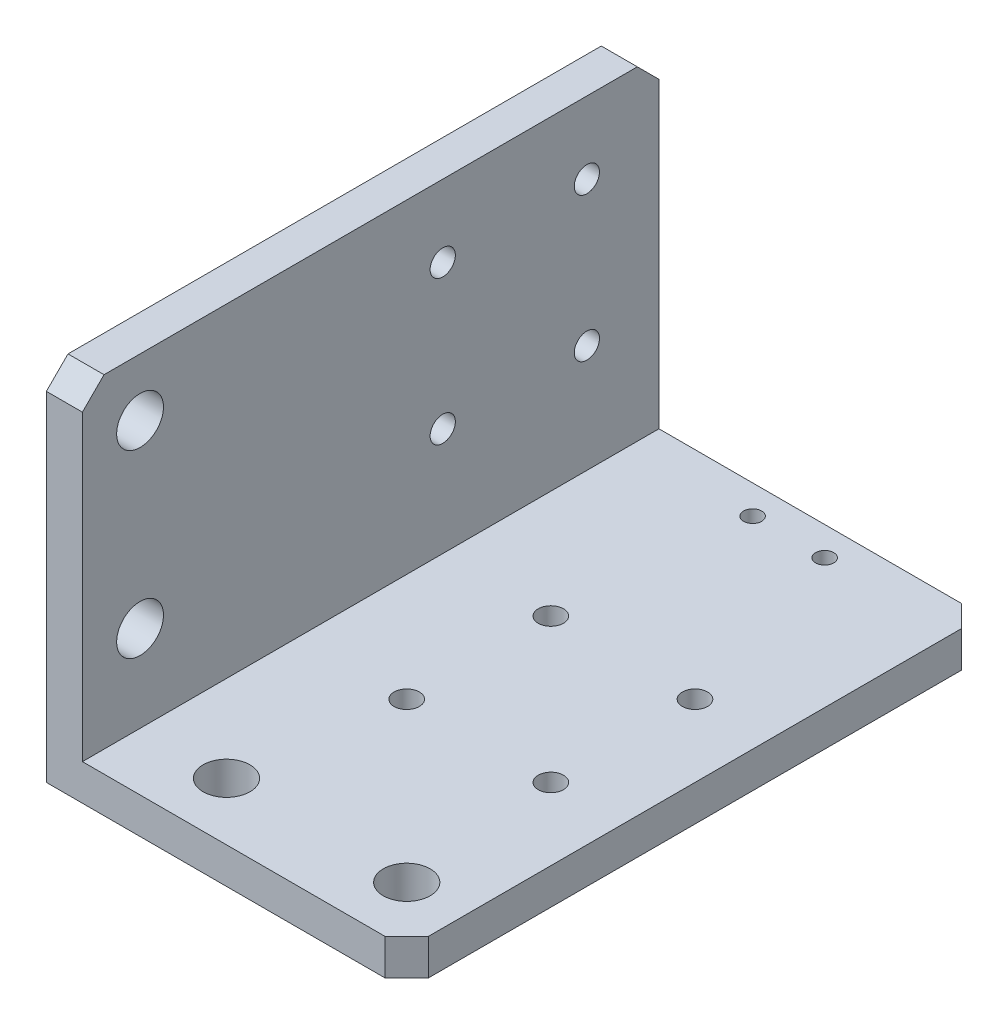
SolidWorks part; units mm, degrees
material "Lega 1060"
ref_plane "Piano frontale" through (0, 0, 0) normal (0, 0, 1) x (1, 0, 0)
ref_plane "Piano superiore" through (0, 0, 0) normal (0, 1, 0) x (1, 0, 0)
ref_plane "Piano destro" through (0, 0, 0) normal (1, 0, 0) x (0, 0, -1)
sketch "Schizzo1" plane through (0, 0, 0) normal (0, 0, 1) x (1, 0, 0)
  line L0 (0, 0) -> (0, 50)
  line L1 (0, 50) -> (5, 50)
  line L2 (5, 50) -> (5, 5)
  line L3 (5, 5) -> (50, 5)
  line L4 (50, 5) -> (50, 0)
  line L5 (50, 0) -> (0, 0)
  dimension "D1" = 5
  dimension "D2" = 5
  dimension "D3" = 50
  dimension "D4" = 50
extrude "Estrusione-Estrusione1" add sketch "Schizzo1" along normal blind 80
sketch "Schizzo2" plane through (0, 0, 0) normal (0, -1, 0) x (1, 0, 0)
  line L0 (5.4524, 72) -> (42.7933, 72) construction
  line L1 (0, 80) -> (50, 80) construction
  line L5 (50, 80) -> (50, 0) construction
  point P4 (17, 72)
  point P5 (42, 72)
  dimension "D1" = 8
  dimension "D2" = 25
  dimension "D3" = 8
sketch "Schizzo3" plane through (0, 0, 0) normal (-1, 0, 0) x (0, 0, 1)
  line L0 (72, 44.621) -> (72, 5.772) construction
  line L1 (80, 50) -> (80, 0) construction
  line L2 (80, 50) -> (0, 50) construction
  point P4 (72, 42)
  point P5 (72, 17)
  dimension "D1" = 8
  dimension "D2" = 8
  dimension "D3" = 25
hole_wizard "Foro Ø6.5 (6.5)-1" positions "Schizzo5" profile "Schizzo4" hole size "Ø6.5" standard "ISO" end condition through all
sketch "Schizzo5" plane through (0, 0, 0) normal (0, -1, 0) x (-1, 0, 0)
  point P0 (-17, -72)
  point P3 (-42, -72)
sketch "Schizzo4" plane through (17, 0, 72) normal (1, 0, 0) x (0, 0, -1)
  line L0 (0, 0) -> (0, 50)
  line L1 (0, 50) -> (3.25, 50)
  line L2 (3.25, 50) -> (3.25, 0)
  line L5 (3.25, 0) -> (0, 0)
  line L11 (0, -6.35) -> (0, 107.95) construction
  dimension "Thru Hole Dia." = 6.5
  dimension "Thru Hole Depth" = 50
hole_wizard "Foro Ø6.5 (6.5)-2" positions "Schizzo7" profile "Schizzo6" hole size "Ø6.5" standard "ISO"
sketch "Schizzo7" plane through (0, 0, 0) normal (-1, 0, 0) x (0, 0, 1)
  point P1 (72, 42)
  point P4 (72, 17)
sketch "Schizzo6" plane through (0, 42, 72) normal (0, 1, 0) x (0, 0, 1)
  line L0 (0, 0) -> (0, 6.9528)
  line L1 (0, 6.9528) -> (3.25, 5)
  line L2 (3.25, 5) -> (3.25, 0)
  line L5 (3.25, 0) -> (0, 0)
  line L10 (0, 6.9528) -> (-3.25, 5) construction
  line L11 (0, -6.35) -> (0, 107.95) construction
  dimension "Hole Dia." = 6.5
  dimension "Hole Depth" = 5
  dimension "Drill Angle" = 118
ref_plane "Piano1" through (0, 0, 40) normal (0, 0, 1) x (1, 0, 0)
sketch "Schizzo8" plane through (0, 0, 0) normal (-1, 0, 0) x (0, 0, 1)
  line L2 (80, 50) -> (80, 0) construction
  line L3 (80, 50) -> (0, 50) construction
  circle A0 centre (20, 30) radius 7
  dimension "D3" = 14
  dimension "D1" = 60
  dimension "D2" = 20
sketch "Schizzo9" plane through (0, 0, 0) normal (0, -1, 0) x (1, 0, 0)
  line L0 (50, 80) -> (50, 0) construction
  line L1 (0, 80) -> (50, 80) construction
  circle A0 centre (30, 40) radius 7
  dimension "D1" = 14
  dimension "D2" = 20
  dimension "D3" = 40
sketch "Schizzo10" plane through (0, 0, 0) normal (-1, 0, 0) x (0, 0, 1)
  line L1 (20, 42.2663) -> (20, 14.8621) construction
  line L2 (19.1906, 30.8094) -> (20, 30) construction
  circle A0 centre (10, 40) radius 1.75
  circle A1 centre (30, 40) radius 1.75
  circle A3 centre (30, 20) radius 1.75
  circle A4 centre (10, 20) radius 1.75
  circle A5 centre (20, 30) radius 7 construction
  point P20 (20, 30)
  dimension "D1" = 3.5
  dimension "D2" = 20
  dimension "D3" = 45
  dimension "D4" = 4
extrude "Taglio-Estrusione3" cut sketch "Schizzo10" against normal up to next
sketch "Schizzo11" plane through (0, 0, 0) normal (0, -1, 0) x (1, 0, 0)
  line L0 (30, 40) -> (14.4837, 40) construction
  line L1 (30, 40) -> (34.5929, 44.5929) construction
  circle A0 centre (20, 30) radius 1.75
  circle A3 centre (20, 50) radius 1.75
  circle A4 centre (40, 50) radius 1.75
  circle A5 centre (40, 30) radius 1.75
  circle A6 centre (30, 40) radius 7 construction
  point P2 (30, 40)
  point P17 (30, 40)
  dimension "D2" = 3.5
  dimension "D1" = 20
  dimension "D3" = 45
  dimension "D4" = 4
extrude "Taglio-Estrusione4" cut sketch "Schizzo11" against normal up to next
chamfer "Smusso1" distance 3 angle 45 4 edges at (2.5, 50, 0) (50, 2.5, 0) (2.5, 50, 80) (50, 2.5, 80)
sketch "Schizzo12" plane through (0, 5, 0) normal (0, 1, 0) x (1, 0, 0)
  line L0 (50, -77) -> (50, -3) construction
  line L1 (47, 0) -> (5, 0) construction
  circle A0 centre (32, -4) radius 1.25
  circle A1 centre (22, -4) radius 1.25
  dimension "D1" = 2.5
  dimension "D3" = 18
  dimension "D4" = 4
  dimension "D2" = 10
extrude "Taglio-Estrusione5" cut sketch "Schizzo12" against normal up to next
